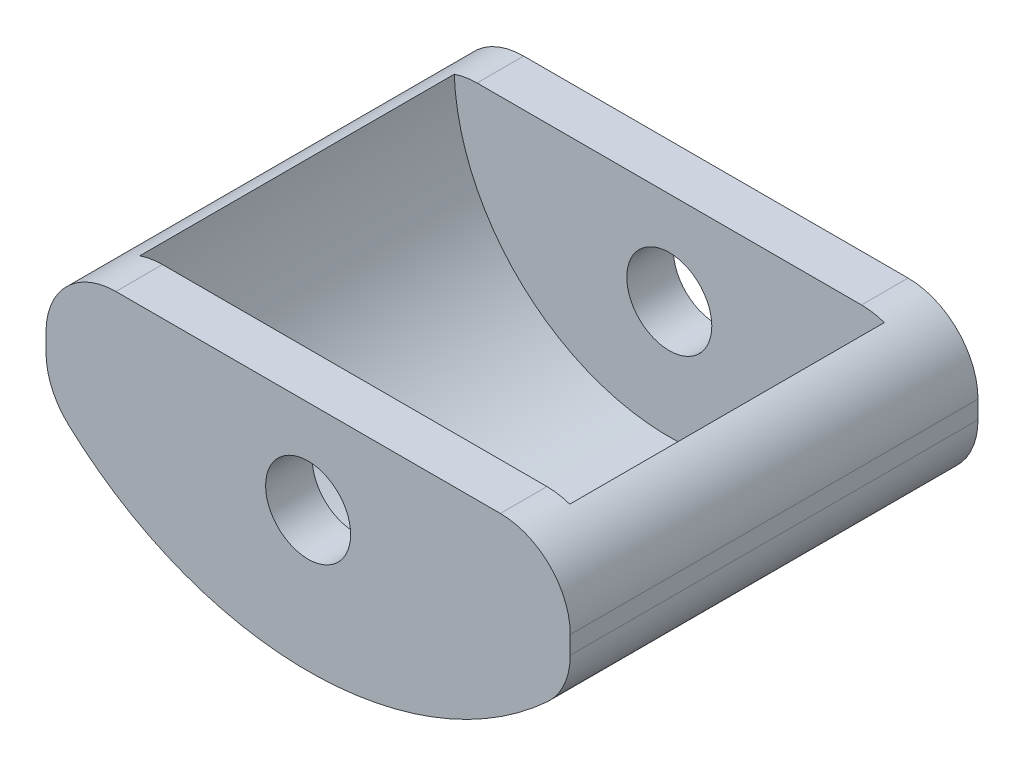
SolidWorks part; units mm, degrees
ref_plane "Front Plane" through (0, 0, 0) normal (0, 0, 1) x (1, 0, 0)
ref_plane "Top Plane" through (0, 0, 0) normal (0, 1, 0) x (1, 0, 0)
ref_plane "Right Plane" through (0, 0, 0) normal (1, 0, 0) x (0, 0, -1)
sketch "Sketch1" plane through (0, 0, 0) normal (0, 1, 0) x (1, 0, 0)
  line L1 (-11.25, 8.75) -> (11.25, 8.75)
  line L2 (-11.25, 8.75) -> (-11.25, -8.75)
  line L3 (-11.25, -8.75) -> (11.25, -8.75)
  line L4 (11.25, 8.75) -> (11.25, -8.75)
  dimension "D1" = 17.5
  dimension "D2" = 8.75
  dimension "D3" = 22.5
  dimension "D4" = 11.25
extrude "Boss-Extrude1" add sketch "Sketch1" along normal blind 10
sketch "Sketch2" plane through (0, 0, 8.75) normal (0, 0, 1) x (1, 0, 0)
  line L0 (-11.25, 10) -> (-11.25, 0) construction
  line L1 (11.25, 10) -> (11.25, 0) construction
  line L2 (-11.25, 5) -> (-11.25, 0)
  line L3 (-11.25, 0) -> (11.25, 0)
  line L4 (11.25, 0) -> (11.25, 5)
  line L5 (-11.25, 10) -> (11.25, 10) construction
  arc A0 (-11.25, 5) -> (11.25, 5) centre (0, 15.1866) ccw
  circle A1 centre (0, 6) radius 1.825
  point P19 (0, 0.01)
  dimension "D1" = 3.65
  dimension "D2" = 11.25
  dimension "D3" = 4
  dimension "D4" = 5.99
extrude "Cut-Extrude1" cut sketch "Sketch2" against normal through all and the other way through all
ref_plane "Plane1" through (0, 0, 6.75) normal (0, 0, 1) x (1, 0, 0)
sketch "Sketch3" plane through (0, 0, 6.75) normal (0, 0, 1) x (1, 0, 0)
  line L5 (-7.5, 10) -> (7.5, 10)
  line L6 (11.25, 10) -> (-11.25, 10) construction
  line L7 (-5.7661, 10.0479) -> (5.7661, 10.0479)
  arc A3 (-7.5, 10) -> (7.5, 10) centre (0, 10.2071) ccw construction
  arc A4 (-9.2339, 9.9521) -> (9.2339, 9.9521) centre (0, 10.2071) ccw
  arc A5 (-5.7661, 10.0479) -> (5.7661, 10.0479) centre (0, 10.2071) ccw
  arc A6 (-5.7661, 10.0479) -> (-9.2339, 9.9521) centre (-7.5, 10) ccw
  arc A7 (9.2339, 9.9521) -> (5.7661, 10.0479) centre (7.5, 10) ccw
  arc A8 (-5.7661, 10.0479) -> (5.7661, 10.0479) centre (0, 10.2071) ccw
  point P5 (0, 2.7043)
  point P16 (0, 10)
  dimension "D3" = 5.7683
  dimension "D1" = 15
  dimension "D2" = 3.75
  dimension "D4" = 7.2957
extrude "Cut-Extrude2" cut sketch "Sketch3" against normal blind 13.5 contours A5 A7 A4 A6
sketch "Sketch4" plane through (0, 10, 0) normal (0, 1, 0) x (1, 0, 0)
  line L1 (-5.7645, 6.75) -> (5.7645, 6.75)
  line L2 (-5.7645, 6.75) -> (-5.7645, -6.75)
  line L3 (-5.7645, -6.75) -> (5.7645, -6.75)
  line L4 (5.7645, 6.75) -> (5.7645, -6.75)
extrude "Cut-Extrude3" cut sketch "Sketch4" against normal up to surface (7.011 mm away) up to face at (0, 5.4609, 0)
fillet "Fillet1" radius 3 4 edges at (11.25, 5, 0) (-11.25, 5, 0) (11.25, 10, 0) (-11.25, 10, 0)
